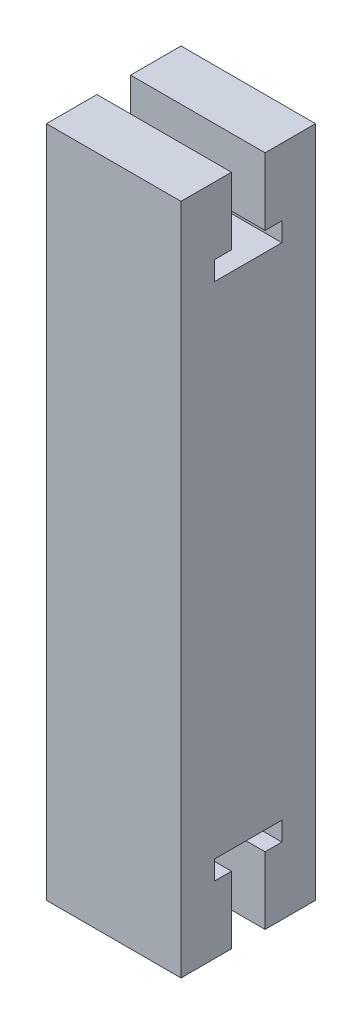
SolidWorks part; units mm, degrees
ref_plane "Front Plane" through (0, 0, 0) normal (0, 0, 1) x (1, 0, 0)
ref_plane "Top Plane" through (0, 0, 0) normal (0, 1, 0) x (1, 0, 0)
ref_plane "Right Plane" through (0, 0, 0) normal (1, 0, 0) x (0, 0, -1)
sketch "Sketch1" plane through (0, 0, 0) normal (0, 1, 0) x (1, 0, 0)
  line L1 (0, 0) -> (20, 0)
  line L2 (0, 0) -> (0, -20)
  line L3 (0, -20) -> (20, -20)
  line L4 (20, 0) -> (20, -20)
extrude "Boss-Extrude1" add sketch "Sketch1" along normal blind 50 and the other way blind 50
sketch "Sketch3" plane through (0, 0, 0) normal (-1, 0, 0) x (0, 0, 1)
  line L1 (7.5, 40) -> (5, 40)
  line L8 (12.5, 40) -> (15, 40)
  line L10 (10, 50) -> (7.5, 50)
  line L11 (15, 40) -> (15, 37.1712)
  line L12 (0, 50) -> (20, 50) construction
  line L13 (10, 50) -> (12.5, 50)
  line L14 (12.5, 50) -> (12.5, 40)
  line L15 (7.5, 50) -> (7.5, 40)
  line L16 (15, 37.1712) -> (5, 37.1712)
  line L17 (5, 37.1712) -> (5, 40)
  line L18 (0, 0) -> (20, 0) construction
  line L30 (20, -50) -> (20, 50) construction
  line L31 (5, -37.1712) -> (5, -40)
  line L32 (15, -37.1712) -> (5, -37.1712)
  line L33 (7.5, -50) -> (7.5, -40)
  line L34 (12.5, -50) -> (12.5, -40)
  line L35 (10, -50) -> (12.5, -50)
  line L36 (15, -40) -> (15, -37.1712)
  line L37 (10, -50) -> (7.5, -50)
  line L38 (12.5, -40) -> (15, -40)
  line L39 (7.5, -40) -> (5, -40)
extrude "Cut-Extrude2" cut sketch "Sketch3" against normal through all
